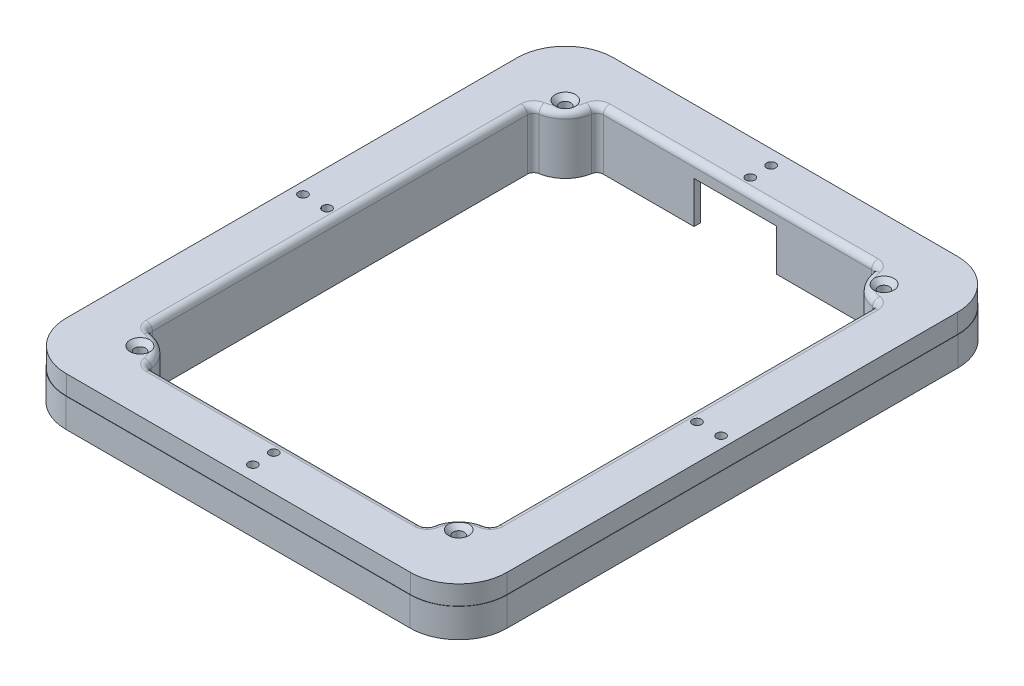
SolidWorks part; units mm, degrees
ref_plane "Front Plane" through (0, 0, 0) normal (0, 0, 1) x (1, 0, 0)
ref_plane "Top Plane" through (0, 0, 0) normal (0, 1, 0) x (1, 0, 0)
ref_plane "Right Plane" through (0, 0, 0) normal (1, 0, 0) x (0, 0, -1)
sketch "Sketch1" plane through (0, 0, 0) normal (0, 1, 0) x (1, 0, 0)
  line L0 (-11, 72.2) -> (-47.6, 72.2) construction
  line L1 (-45.6, -72.2) -> (45.6, -72.2)
  line L2 (-55.6, -62.2) -> (-55.6, 62.2)
  line L3 (-45.6, 72.2) -> (45.6, 72.2)
  line L4 (55.6, -62.2) -> (55.6, 62.2)
  line L5 (-55.6, -72.2) -> (55.6, 72.2) construction
  line L6 (-55.6, 72.2) -> (55.6, -72.2) construction
  line L7 (-43.6, -70.2) -> (43.6, -70.2)
  line L8 (-53.6, -60.2) -> (-53.6, 60.2)
  line L9 (-43.6, 70.2) -> (43.6, 70.2)
  line L10 (53.6, -60.2) -> (53.6, 60.2)
  line L11 (-53.6, -70.2) -> (53.6, 70.2) construction
  line L12 (-53.6, 70.2) -> (53.6, -70.2) construction
  line L13 (-55.6, 64.2) -> (-55.6, -64.2) construction
  arc A0 (-43.6, -70.2) -> (-53.6, -60.2) centre (-43.6, -60.2) cw
  arc A1 (-45.6, -72.2) -> (-55.6, -62.2) centre (-45.6, -62.2) cw
  arc A2 (43.6, -70.2) -> (53.6, -60.2) centre (43.6, -60.2) ccw
  arc A3 (45.6, -72.2) -> (55.6, -62.2) centre (45.6, -62.2) ccw
  arc A4 (43.6, 70.2) -> (53.6, 60.2) centre (43.6, 60.2) cw
  arc A5 (45.6, 72.2) -> (55.6, 62.2) centre (45.6, 62.2) cw
  arc A6 (-53.6, 60.2) -> (-43.6, 70.2) centre (-43.6, 60.2) cw
  arc A7 (-55.6, 62.2) -> (-45.6, 72.2) centre (-45.6, 62.2) cw
  point P0 (0, 0)
  point P5 (0, 0)
  point P11 (0, 0)
  dimension "D3" = 10
  dimension "D1" = 2
  dimension "D2" = 2
extrude "Boss-Extrude1" add sketch "Sketch1" along normal blind 13
sketch "Sketch8" plane through (0, 0, 0) normal (0, -1, 0) x (1, 0, 0)
  arc A0 (-53.6, -60.2) -> (-43.6, -70.2) centre (-43.6, -60.2) ccw construction
  arc A1 (43.6, -70.2) -> (53.6, -60.2) centre (43.6, -60.2) ccw construction
  arc A2 (53.6, 60.2) -> (43.6, 70.2) centre (43.6, 60.2) ccw construction
  arc A3 (-43.6, 70.2) -> (-53.6, 60.2) centre (-43.6, 60.2) ccw construction
  arc A4 (-53.6, -60.2) -> (-43.6, -70.2) centre (-43.6, -60.2) ccw
  arc A5 (43.6, -70.2) -> (53.6, -60.2) centre (43.6, -60.2) ccw
  arc A6 (53.6, 60.2) -> (43.6, 70.2) centre (43.6, 60.2) ccw
  arc A7 (-43.6, 70.2) -> (-53.6, 60.2) centre (-43.6, 60.2) ccw
  arc A8 (-53.6, -60.2) -> (-43.6, -70.2) centre (-53.6, -70.2) cw
  arc A9 (53.6, -60.2) -> (43.6, -70.2) centre (53.6, -70.2) ccw
  arc A10 (43.6, 70.2) -> (53.6, 60.2) centre (53.6, 70.2) ccw
  arc A11 (-43.6, 70.2) -> (-53.6, 60.2) centre (-53.6, 70.2) cw
  dimension "D1" = 10
extrude "Boss-Extrude6" add sketch "Sketch8" against normal through all
ref_axis "Axis1" through (0, 10.5, 0) along (0, -1, 0)
sketch "Sketch2" plane through (0, 13, 0) normal (0, 1, 0) x (1, 0, 0)
  line L0 (53.6, -60.2) -> (53.6, 60.2) construction
  line L1 (-43.6, -70.2) -> (43.6, -70.2) construction
  line L2 (-53.6, 60.2) -> (-53.6, -60.2) construction
  line L3 (43.6, 70.2) -> (-43.6, 70.2) construction
  line L4 (53.6, -60.2) -> (53.6, 60.2)
  line L5 (-43.6, -70.2) -> (43.6, -70.2)
  line L6 (-53.6, 60.2) -> (-53.6, -60.2)
  line L7 (43.6, 70.2) -> (-43.6, 70.2)
  line L8 (51.604, 100.2) -> (-51.604, 100.2)
  line L9 (-83.6, 68.204) -> (-83.6, -68.204)
  line L10 (-51.604, -100.2) -> (51.604, -100.2)
  line L11 (83.6, -68.204) -> (83.6, 68.204)
  arc A8 (-51.604, 100.2) -> (-83.6, 68.204) centre (-20.7612, 37.3612) ccw
  arc A9 (-83.6, -68.204) -> (-51.604, -100.2) centre (-20.7612, -37.3612) ccw
  arc A10 (51.604, -100.2) -> (83.6, -68.204) centre (20.7612, -37.3612) ccw
  arc A11 (83.6, 68.204) -> (51.604, 100.2) centre (20.7612, 37.3612) ccw
  arc A12 (53.6, 60.2) -> (43.6, 70.2) centre (20.7612, 37.3612) ccw construction
  arc A13 (-43.6, 70.2) -> (-53.6, 60.2) centre (-20.7612, 37.3612) ccw construction
  arc A14 (-53.6, -60.2) -> (-43.6, -70.2) centre (-20.7612, -37.3612) ccw construction
  arc A15 (43.6, -70.2) -> (53.6, -60.2) centre (20.7612, -37.3612) ccw construction
  arc A16 (-53.6, 60.2) -> (-43.6, 70.2) centre (-53.6, 70.2) ccw construction
  arc A17 (43.6, 70.2) -> (53.6, 60.2) centre (53.6, 70.2) ccw construction
  arc A18 (53.6, -60.2) -> (43.6, -70.2) centre (53.6, -70.2) ccw construction
  arc A19 (-43.6, -70.2) -> (-53.6, -60.2) centre (-53.6, -70.2) ccw construction
  arc A20 (-53.6, 60.2) -> (-43.6, 70.2) centre (-53.6, 70.2) ccw
  arc A21 (43.6, 70.2) -> (53.6, 60.2) centre (53.6, 70.2) ccw
  arc A22 (53.6, -60.2) -> (43.6, -70.2) centre (53.6, -70.2) ccw
  arc A23 (-43.6, -70.2) -> (-53.6, -60.2) centre (-53.6, -70.2) ccw
  dimension "D1" = 30
extrude "Boss-Extrude2" add sketch "Sketch2" along normal blind 5
sketch "Sketch3" plane through (0, 13, 0) normal (0, -1, 0) x (1, 0, 0)
  line L0 (-59.6, -64.2) -> (-59.6, 64.2) construction
  line L1 (53.6, 83.2) -> (-53.6, 83.2)
  line L2 (66.6, 70.2) -> (66.6, -70.2)
  line L3 (53.6, -83.2) -> (-53.6, -83.2)
  line L4 (-66.6, 70.2) -> (-66.6, -70.2)
  line L5 (66.6, 83.2) -> (-66.6, -83.2) construction
  line L6 (66.6, -83.2) -> (-66.6, 83.2) construction
  line L7 (-11, -76.2) -> (-47.6, -76.2) construction
  line L8 (-68.6, 70.2) -> (-68.6, -70.2)
  line L9 (53.6, -85.2) -> (-53.6, -85.2)
  line L10 (68.6, 70.2) -> (68.6, -70.2)
  line L11 (53.6, 85.2) -> (-53.6, 85.2)
  line L12 (-66.6, 0) -> (-59.6, 0) construction
  line L13 (-29.35, -76.2) -> (-29.35, -83.2) construction
  arc A0 (66.6, -70.2) -> (53.6, -83.2) centre (53.6, -70.2) cw
  arc A1 (53.6, 83.2) -> (66.6, 70.2) centre (53.6, 70.2) cw
  arc A2 (-53.6, 83.2) -> (-66.6, 70.2) centre (-53.6, 70.2) ccw
  arc A3 (-53.6, -83.2) -> (-66.6, -70.2) centre (-53.6, -70.2) cw
  arc A4 (-53.6, -85.2) -> (-68.6, -70.2) centre (-53.6, -70.2) cw
  arc A5 (68.6, -70.2) -> (53.6, -85.2) centre (53.6, -70.2) cw
  arc A6 (53.6, 85.2) -> (68.6, 70.2) centre (53.6, 70.2) cw
  arc A7 (-53.6, 85.2) -> (-68.6, 70.2) centre (-53.6, 70.2) ccw
  point P0 (0, 0)
  dimension "D1" = 13
  dimension "D3" = 7
  dimension "D4" = 2
extrude "Boss-Extrude3" add sketch "Sketch3" along normal blind 3
sketch "Sketch4" plane through (0, 13, 0) normal (0, -1, 0) x (1, 0, 0)
  line L0 (68.6, -70.2) -> (68.6, 70.2) construction
  line L1 (-53.6, -85.2) -> (53.6, -85.2) construction
  line L2 (-68.6, 70.2) -> (-68.6, -70.2) construction
  line L3 (53.6, 85.2) -> (-53.6, 85.2) construction
  line L4 (68.6, -70.2) -> (68.6, 70.2)
  line L5 (-53.6, -85.2) -> (53.6, -85.2)
  line L6 (-68.6, 70.2) -> (-68.6, -70.2)
  line L7 (53.6, 85.2) -> (-53.6, 85.2)
  line L9 (186.2129, -169.3189) -> (-186.2129, -169.3189)
  line L10 (186.2129, -169.3189) -> (186.2129, 169.3189)
  line L11 (186.2129, 169.3189) -> (-186.2129, 169.3189)
  line L12 (-186.2129, -169.3189) -> (-186.2129, 169.3189)
  line L13 (186.2129, -169.3189) -> (-186.2129, 169.3189) construction
  line L14 (186.2129, 169.3189) -> (-186.2129, -169.3189) construction
  arc A0 (68.6, 70.2) -> (53.6, 85.2) centre (53.6, 70.2) ccw construction
  arc A1 (53.6, -85.2) -> (68.6, -70.2) centre (53.6, -70.2) ccw construction
  arc A2 (-68.6, -70.2) -> (-53.6, -85.2) centre (-53.6, -70.2) ccw construction
  arc A3 (-53.6, 85.2) -> (-68.6, 70.2) centre (-53.6, 70.2) ccw construction
  arc A4 (68.6, 70.2) -> (53.6, 85.2) centre (53.6, 70.2) ccw
  arc A5 (53.6, -85.2) -> (68.6, -70.2) centre (53.6, -70.2) ccw
  arc A6 (-68.6, -70.2) -> (-53.6, -85.2) centre (-53.6, -70.2) ccw
  arc A7 (-53.6, 85.2) -> (-68.6, 70.2) centre (-53.6, 70.2) ccw
  point P4 (0, 0)
extrude "Cut-Extrude1" cut sketch "Sketch4" against normal through all
sketch "Sketch5" plane through (0, 18, 0) normal (0, 1, 0) x (1, 0, 0)
  line L0 (-65.1, 0) -> (-57.6, 0) construction
  line L1 (-57.6, 74.2) -> (57.6, 74.2) construction
  line L2 (-57.6, 74.2) -> (-57.6, -74.2) construction
  line L3 (-57.6, -74.2) -> (57.6, -74.2) construction
  line L4 (57.6, 74.2) -> (57.6, -74.2) construction
  line L5 (0, 80.7) -> (0, 74.2) construction
  line L6 (43.6, 70.2) -> (-43.6, 70.2) construction
  line L7 (-53.6, 60.2) -> (-53.6, -60.2) construction
  circle A0 centre (-65.1, 0) radius 1.7 construction
  circle A1 centre (0, 80.7) radius 1.7 construction
  circle A2 centre (65.1, 0) radius 1.7 construction
  circle A3 centre (0, -80.7) radius 1.7 construction
  circle A4 centre (-65.1, 0) radius 1.7 construction
  circle A5 centre (0, 80.7) radius 1.7 construction
  circle A6 centre (65.1, 0) radius 1.7 construction
  circle A7 centre (0, -80.7) radius 1.7 construction
  circle A8 centre (0, 80.7) radius 1.4
  circle A9 centre (-65.1, 0) radius 1.4
  circle A10 centre (0, -80.7) radius 1.4
  circle A11 centre (65.1, 0) radius 1.4
  circle A12 centre (0, 74.2) radius 1.4
  circle A13 centre (-57.6, 0) radius 1.4
  circle A14 centre (57.6, 0) radius 1.4
  circle A15 centre (0, -74.2) radius 1.4
  dimension "D1" = 2.8
  dimension "D2" = 4
  dimension "D3" = 4
extrude "Cut-Extrude2" cut sketch "Sketch5" against normal through all
fillet "Fillet2" radius 2 16 edges at (0, 18, -70.2) (53.6, 18, 0) (0, 18, 70.2) (-53.6, 18, 0) (-43.6, 9, -70.2) (-53.6, 9, -60.2) (43.6, 9, -70.2) (53.6, 9, -60.2) (53.6, 9, 60.2) (43.6, 9, 70.2) (-53.6, 9, 60.2) (-43.6, 9, 70.2) (46.5289, 18, -63.1289) (46.5289, 18, 63.1289) (-46.5289, 18, -63.1289) (-46.5289, 18, 63.1289)
sketch "Sketch6" plane through (0, 0, 0) normal (0, -1, 0) x (1, 0, 0)
  line L0 (41.7678, -70.2) -> (-41.7678, -70.2) construction
  line L1 (-13.5145, -78.8961) -> (12.1759, -78.8961)
  line L2 (-13.5145, -78.8961) -> (-13.5145, -70.2)
  line L3 (-13.5145, -70.2) -> (12.1759, -70.2)
  line L4 (12.1759, -78.8961) -> (12.1759, -70.2)
extrude "Cut-Extrude3" cut sketch "Sketch6" against normal up to surface (13 mm away) up to face at (0, 13, -79.3)
fillet "Fillet3" radius 1 8 edges at (0, 13, -83.2) (-62.7924, 13, -79.3924) (-66.6, 13, 0) (-62.7924, 13, 79.3924) (0, 13, 83.2) (62.7924, 13, 79.3924) (66.6, 13, 0) (62.7924, 13, -79.3924)
sketch "Sketch7" plane through (0, 10, 0) normal (0, -1, 0) x (1, 0, 0)
  line L0 (-53.6, -85.2) -> (53.6, -85.2) construction
  line L1 (68.6, -70.2) -> (68.6, 70.2) construction
  line L2 (-68.6, 70.2) -> (-68.6, -70.2) construction
  line L3 (53.6, 85.2) -> (-53.6, 85.2) construction
  line L4 (-53.6, -85.2) -> (53.6, -85.2)
  line L5 (68.6, -70.2) -> (68.6, 70.2)
  line L6 (-68.6, 70.2) -> (-68.6, -70.2)
  line L7 (53.6, 85.2) -> (-53.6, 85.2)
  line L8 (-68.7, 70.2) -> (-68.7, -70.2)
  line L9 (-53.6, -85.3) -> (53.6, -85.3)
  line L10 (68.7, -70.2) -> (68.7, 70.2)
  line L11 (53.6, 85.3) -> (-53.6, 85.3)
  arc A0 (-68.6, -70.2) -> (-53.6, -85.2) centre (-53.6, -70.2) ccw construction
  arc A1 (53.6, -85.2) -> (68.6, -70.2) centre (53.6, -70.2) ccw construction
  arc A2 (68.6, 70.2) -> (53.6, 85.2) centre (53.6, 70.2) ccw construction
  arc A3 (-53.6, 85.2) -> (-68.6, 70.2) centre (-53.6, 70.2) ccw construction
  arc A4 (-68.6, -70.2) -> (-53.6, -85.2) centre (-53.6, -70.2) ccw
  arc A5 (53.6, -85.2) -> (68.6, -70.2) centre (53.6, -70.2) ccw
  arc A6 (68.6, 70.2) -> (53.6, 85.2) centre (53.6, 70.2) ccw
  arc A7 (-53.6, 85.2) -> (-68.6, 70.2) centre (-53.6, 70.2) ccw
  arc A8 (-53.6, 85.3) -> (-68.7, 70.2) centre (-53.6, 70.2) ccw
  arc A9 (-68.7, -70.2) -> (-53.6, -85.3) centre (-53.6, -70.2) ccw
  arc A10 (53.6, -85.3) -> (68.7, -70.2) centre (53.6, -70.2) ccw
  arc A11 (68.7, 70.2) -> (53.6, 85.3) centre (53.6, 70.2) ccw
  dimension "D1" = 0.1
extrude "Boss-Extrude4" add sketch "Sketch7" along normal blind 7 and the other way blind 2
sketch "Sketch9" plane through (0, 18, 0) normal (0, 1, 0) x (1, 0, 0)
  line L0 (-55.6, -58.3678) -> (-55.6, 58.3678) construction
  line L1 (-49.6, 66.2) -> (49.6, 66.2) construction
  line L2 (-49.6, 66.2) -> (-49.6, -66.2) construction
  line L3 (-49.6, -66.2) -> (49.6, -66.2) construction
  line L4 (49.6, 66.2) -> (49.6, -66.2) construction
  line L5 (-41.7678, 72.2) -> (41.7678, 72.2) construction
  line L6 (55.6, 58.3678) -> (55.6, -58.3678) construction
  line L7 (41.7678, -72.2) -> (-41.7678, -72.2) construction
  circle A0 centre (49.6, 66.2) radius 1.7
  circle A1 centre (-49.6, 66.2) radius 1.7
  circle A2 centre (-49.6, -66.2) radius 1.7
  circle A3 centre (49.6, -66.2) radius 1.7
  point P8 (52.2878, 69.2421)
  point P9 (-52.9419, 69.6407)
  point P17 (-52.2159, 69.2)
  dimension "D1" = 6
  dimension "D2" = 3.4
  dimension "D3" = 6
  dimension "D4" = 6
  dimension "D5" = 6
extrude "Cut-Extrude4" cut sketch "Sketch9" against normal through all
hole_wizard "CSK for M3 Flat Head Machine Screw1" positions "3DSketch1" profile "Sketch10" countersink size "M3" standard "ANSI Metric" end condition through all
sketch3d "3DSketch1"
  line L0 (-49.6, 0, -66.2) -> (-49.6, 18, -66.2) construction
  line L1 (49.6, 0, -66.2) -> (49.6, 18, -66.2) construction
  line L2 (49.6, 0, 66.2) -> (49.6, 18, 66.2) construction
  line L3 (-49.6, 0, 66.2) -> (-49.6, 18, 66.2) construction
  point P0 (-49.6, 18, -66.2)
  point P4 (49.6, 18, -66.2)
  point P8 (49.6, 18, 66.2)
  point P12 (-49.6, 18, 66.2)
sketch "Sketch10" plane through (-49.6, 18, -66.2) normal (1, 0, 0) x (0, 0, 1)
  line L0 (0, 0) -> (0, 18)
  line L1 (0, 18) -> (1.7, 18)
  line L2 (1.7, 18) -> (1.7, 1.45)
  line L3 (1.7, 1.45) -> (3.15, 0)
  line L5 (3.15, 0) -> (0, 0)
  line L6 (-1.7, 1.45) -> (-3.15, 0) construction
  line L11 (0, -6.35) -> (0, 107.95) construction
  dimension "Thru Hole Dia." = 3.4
  dimension "Thru Hole Depth" = 18
  dimension "Near C'Sink Dia." = 6.3
  dimension "Near C'Sink Angle" = 90
